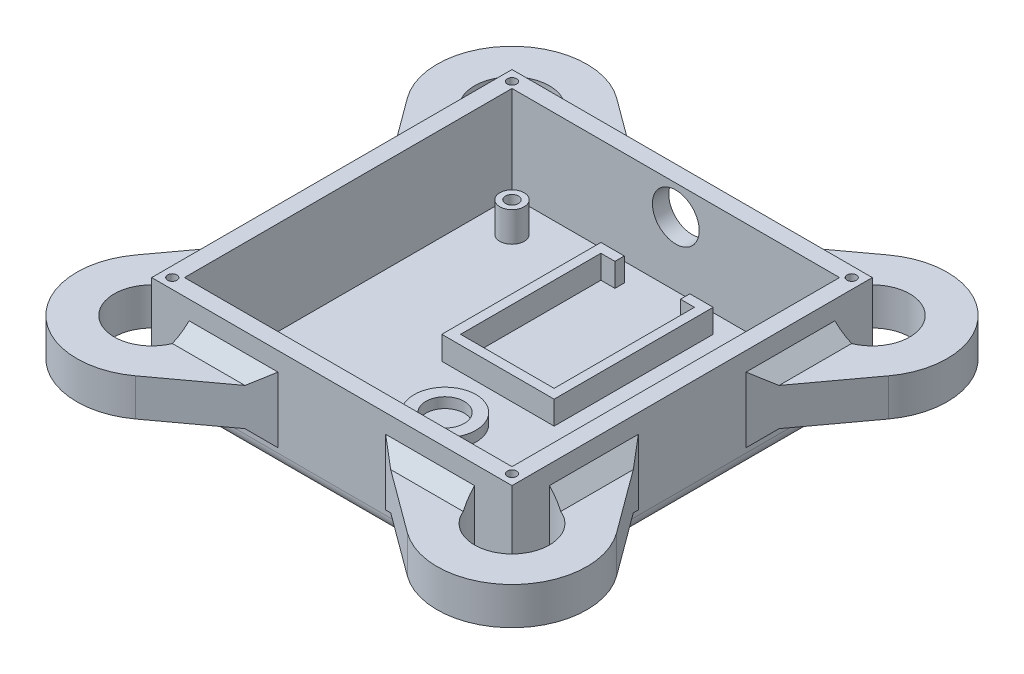
SolidWorks part; units mm, degrees
ref_plane "Front Plane" through (0, 0, 0) normal (0, 0, 1) x (1, 0, 0)
ref_plane "Top Plane" through (0, 0, 0) normal (0, 1, 0) x (1, 0, 0)
ref_plane "Right Plane" through (0, 0, 0) normal (1, 0, 0) x (0, 0, -1)
sketch "Sketch1" plane through (0, 0, 0) normal (0, 1, 0) x (1, 0, 0)
  line L0 (0, 38.5) -> (0, -38.5) construction
  line L2 (-35, 35) -> (35, 35)
  line L3 (35, 35) -> (35, -35)
  line L5 (-35, -35) -> (35, -35)
  line L6 (-35, 35) -> (-35, -35)
  line L7 (-38.5, 0) -> (38.5, 0) construction
  line L8 (38.5, 38.5) -> (-38.5, 38.5)
  line L9 (-38.5, 38.5) -> (-38.5, -38.5)
  line L11 (38.5, 38.5) -> (38.5, -38.5)
  line L12 (38.5, -38.5) -> (-38.5, -38.5)
  point P2 (35, 0)
  point P4 (0, 35)
  point P7 (0, 0)
  point P14 (0, 0)
  dimension "D1" = 70
  dimension "D2" = 77
  dimension "D3" = 77
  dimension "D4" = 70
extrude "Boss-Extrude1" add sketch "Sketch1" along normal blind 20 contours L6 L2 L3 L5 L12 L11 L8 L9 region at (37.4111, 0, 0)
sketch "Sketch2" plane through (0, 0, 0) normal (0, -1, 0) x (1, 0, 0)
  line L1 (-38.5, 38.5) -> (38.5, 38.5)
  line L2 (-38.5, 38.5) -> (-38.5, -38.5)
  line L3 (-38.5, -38.5) -> (38.5, -38.5)
  line L4 (38.5, 38.5) -> (38.5, -38.5)
extrude "Boss-Extrude2" add sketch "Sketch2" along normal blind 2
sketch "Sketch3" plane through (0, 0, 0) normal (0, 1, 0) x (1, 0, 0)
  line L0 (0, 35) -> (0, -35) construction
  line L1 (-35, 35) -> (35, 35) construction
  line L2 (-35, -35) -> (35, -35) construction
  line L3 (0, -35) -> (0, 0) construction
  line L4 (0, 0) -> (35, 0) construction
  line L5 (35, 35) -> (35, -35) construction
  line L6 (35, 0) -> (-35, 0) construction
  line L7 (-35, 35) -> (-35, -35) construction
  line L8 (-30, 30) -> (30, 30) construction
  line L9 (30, 30) -> (30, -30) construction
  line L10 (-30, -30) -> (30, -30) construction
  line L11 (-30, 30) -> (-30, -30) construction
  line L14 (-35, 35) -> (35, 35) construction
  circle A0 centre (28, 28) radius 2.6
  circle A1 centre (28, 28) radius 1.4
  circle A2 centre (28, -28) radius 2.6
  circle A3 centre (28, -28) radius 1.4
  circle A4 centre (-28, -28) radius 1.4
  circle A5 centre (-28, -28) radius 2.6
  circle A6 centre (-28, 28) radius 2.6
  circle A7 centre (-28, 28) radius 1.4
  point P23 (30, 0)
  point P28 (0, -30)
  point P32 (0, 30)
  dimension "D3" = 2
  dimension "D4" = 5.2
  dimension "D5" = 2.8
  dimension "D1" = 7
  dimension "D2" = 7
extrude "Boss-Extrude3" add sketch "Sketch3" along normal blind 6.4
sketch "Sketch4" plane through (0, 20, 0) normal (0, 1, 0) x (1, 0, 0)
  line L0 (0, 38.5) -> (0, -38.5) construction
  line L1 (-35, 35) -> (35, 35) construction
  line L2 (38.5, -38.5) -> (-38.5, -38.5) construction
  line L3 (-38.5, 0) -> (38.5, 0) construction
  line L4 (-38.5, 38.5) -> (-38.5, -38.5) construction
  line L5 (-38.5, 38.5) -> (-38.5, -38.5) construction
  line L6 (38.5, 38.5) -> (-38.5, 38.5) construction
  line L9 (38.5, 38.5) -> (38.5, -38.5) construction
  circle A1 centre (-36.3, 36.3) radius 1
  circle A2 centre (36.3, 36.3) radius 1
  circle A3 centre (36.3, -36.3) radius 1
  circle A4 centre (-36.3, -36.3) radius 1
  dimension "D1" = 3.5
  dimension "D2" = 2.2
  dimension "D3" = 2.2
extrude "Cut-Extrude1" cut sketch "Sketch4" against normal blind 8
ref_plane "Plane1" through (0, 5, 0) normal (0, -1, 0) x (-1, 0, 0)
sketch "Sketch10" plane through (0, 0, 0) normal (0, 1, 0) x (1, 0, 0)
  line L0 (0, 35) -> (0, -10.2) construction
  line L1 (-35, 35) -> (35, 35) construction
  line L4 (-35, 35) -> (-35, -35) construction
  line L5 (-35, 0) -> (35, 0) construction
  line L6 (35, 35) -> (35, -35) construction
  line L13 (-1.3349, -18.1766) -> (-1.3349, -20.7636)
  line L14 (1.3349, -18.1766) -> (1.3349, -20.7636)
  arc A0 (1.3349, -18.1766) -> (-1.3349, -18.1766) centre (0, -14.3) ccw
  arc A1 (1.3349, -20.7636) -> (-1.3349, -20.7636) centre (0, -14.3) ccw
  dimension "D2" = 8.2
  dimension "D1" = 13.2
  dimension "D3" = 14.3
extrude "Boss-Extrude7" add sketch "Sketch10" along normal blind 2.2
sketch "Sketch11" plane through (0, 0, 0) normal (0, 1, 0) x (1, 0, 0)
  line L0 (12, -1.3684) -> (35, 0) construction
  line L1 (-10, 29) -> (-10, -1)
  line L3 (-12, 31) -> (-12, -3)
  line L5 (35, 35) -> (35, -35) construction
  line L6 (-35, 35) -> (35, 35) construction
  line L7 (-10, 29) -> (-7, 29)
  line L9 (-10, -1) -> (10, -1)
  line L12 (-12, -3) -> (12, -3)
  line L13 (12, -3) -> (12, 31)
  line L14 (12, 31) -> (7, 31)
  line L15 (7, 31) -> (7, 29)
  line L16 (10, 29) -> (10, -1)
  line L17 (0, -1) -> (10, -1)
  line L19 (7, 29) -> (10, 29)
  line L21 (-12, 31) -> (-7, 31)
  line L22 (-7, 31) -> (-7, 29)
  line L23 (-7, 29) -> (-10, 29)
  line L24 (7, 29) -> (10, 29)
  dimension "D1" = 30
  dimension "D2" = 6
  dimension "D3" = 10
  dimension "D4" = 2
  dimension "D5" = 10
  dimension "D6" = 2
  dimension "D7" = 3
  dimension "D8" = 3
  dimension "D9" = 2
  dimension "D10" = 2
  dimension "D11" = 2
fillet "Fillet1" radius 3 4 edges at (0, -2, 38.5) (38.5, -2, 0) (0, -2, -38.5) (-38.5, -2, 0)
extrude "Boss-Extrude8" add sketch "Sketch11" along normal blind 5 contours L22 L21 L3 L12 L13 L14 L15 L19 L16 L9 L1 L7 region at (-10.4162, 0, -14)
sketch "Sketch15" plane through (0, 0, -38.5) normal (0, 0, -1) x (-1, 0, 0)
  line L1 (0, 20) -> (0, 1) construction
  line L3 (-38.5, 20) -> (38.5, 20) construction
  circle A1 centre (0, 13.7) radius 5
  dimension "D1" = 6.3
extrude "Cut-Extrude2" cut sketch "Sketch15" against normal up to surface (3.5 mm away) up to face at (0, 10, -35)
sketch "Sketch17" plane through (0, 5, 0) normal (0, -1, 0) x (-1, 0, 0)
  line L0 (38.5, 22.5) -> (38.5, 11.5)
  line L1 (22.5, 38.5) -> (38.5, 38.5) construction
  line L2 (38.5, 38.5) -> (38.5, 22.5) construction
  line L3 (22.5, 38.5) -> (30.5, 38.5)
  line L4 (38.5, 30.5) -> (38.5, 22.5)
  line L5 (11.5, 38.5) -> (29.0185, 51.388)
  line L6 (-38.5, 38.5) -> (38.5, 38.5) construction
  line L7 (51.388, 29.0185) -> (38.5, 11.5)
  line L8 (38.5, 38.5) -> (38.5, -38.5) construction
  line L9 (11.5, 38.5) -> (22.5, 38.5)
  line L10 (0, 0) -> (0, -35.5) construction
  line L11 (-35.5, -35.5) -> (35.5, -35.5) construction
  line L12 (0, -35.5) -> (0, 0) construction
  line L13 (0, 0) -> (35.5, 0) construction
  line L14 (35.5, -35.5) -> (35.5, 35.5) construction
  line L15 (-38.5, 30.5) -> (-38.5, 22.5)
  line L16 (-22.5, 38.5) -> (-30.5, 38.5)
  line L17 (-11.5, 38.5) -> (-22.5, 38.5)
  line L18 (-11.5, 38.5) -> (-29.0185, 51.388)
  line L19 (-51.388, 29.0185) -> (-38.5, 11.5)
  line L20 (-38.5, 22.5) -> (-38.5, 11.5)
  line L21 (38.5, -30.5) -> (38.5, -22.5)
  line L22 (22.5, -38.5) -> (30.5, -38.5)
  line L23 (11.5, -38.5) -> (22.5, -38.5)
  line L24 (11.5, -38.5) -> (29.0185, -51.388)
  line L25 (51.388, -29.0185) -> (38.5, -11.5)
  line L26 (38.5, -22.5) -> (38.5, -11.5)
  line L27 (-22.5, -38.5) -> (-30.5, -38.5)
  line L28 (-11.5, -38.5) -> (-22.5, -38.5)
  line L29 (-11.5, -38.5) -> (-29.0185, -51.388)
  line L30 (-51.388, -29.0185) -> (-38.5, -11.5)
  line L31 (-38.5, -22.5) -> (-38.5, -11.5)
  line L32 (-38.5, -30.5) -> (-38.5, -22.5)
  arc A2 (38.5, 30.5) -> (30.5, 38.5) centre (38.5, 38.5) ccw
  arc A3 (51.388, 29.0185) -> (29.0185, 51.388) centre (38.5, 38.5) ccw
  arc A4 (-38.5, 30.5) -> (-30.5, 38.5) centre (-38.5, 38.5) cw
  arc A5 (-51.388, 29.0185) -> (-29.0185, 51.388) centre (-38.5, 38.5) cw
  arc A6 (38.5, -30.5) -> (30.5, -38.5) centre (38.5, -38.5) cw
  arc A7 (51.388, -29.0185) -> (29.0185, -51.388) centre (38.5, -38.5) cw
  arc A8 (-38.5, -30.5) -> (-30.5, -38.5) centre (-38.5, -38.5) ccw
  arc A9 (-51.388, -29.0185) -> (-29.0185, -51.388) centre (-38.5, -38.5) ccw
  dimension "D1" = 16
  dimension "D2" = 8
  dimension "D3" = 11
  dimension "D4" = 11
  dimension "D5" = 8
  dimension "D6" = 8
extrude "Boss-Extrude9" add sketch "Sketch17" against normal blind 8
chamfer "Chamfer1" distance 3 angle 45 16 edges at (-38.5, 5, -21) (-38.5, 13, -21) (-21, 13, -38.5) (-21, 5, -38.5) (21, 5, -38.5) (21, 13, -38.5) (38.5, 5, -21) (38.5, 13, -21) (38.5, 13, 21) (38.5, 5, 21) (21, 5, 38.5) (21, 13, 38.5) (-21, 13, 38.5) (-21, 5, 38.5) (-38.5, 5, 21) (-38.5, 13, 21)
